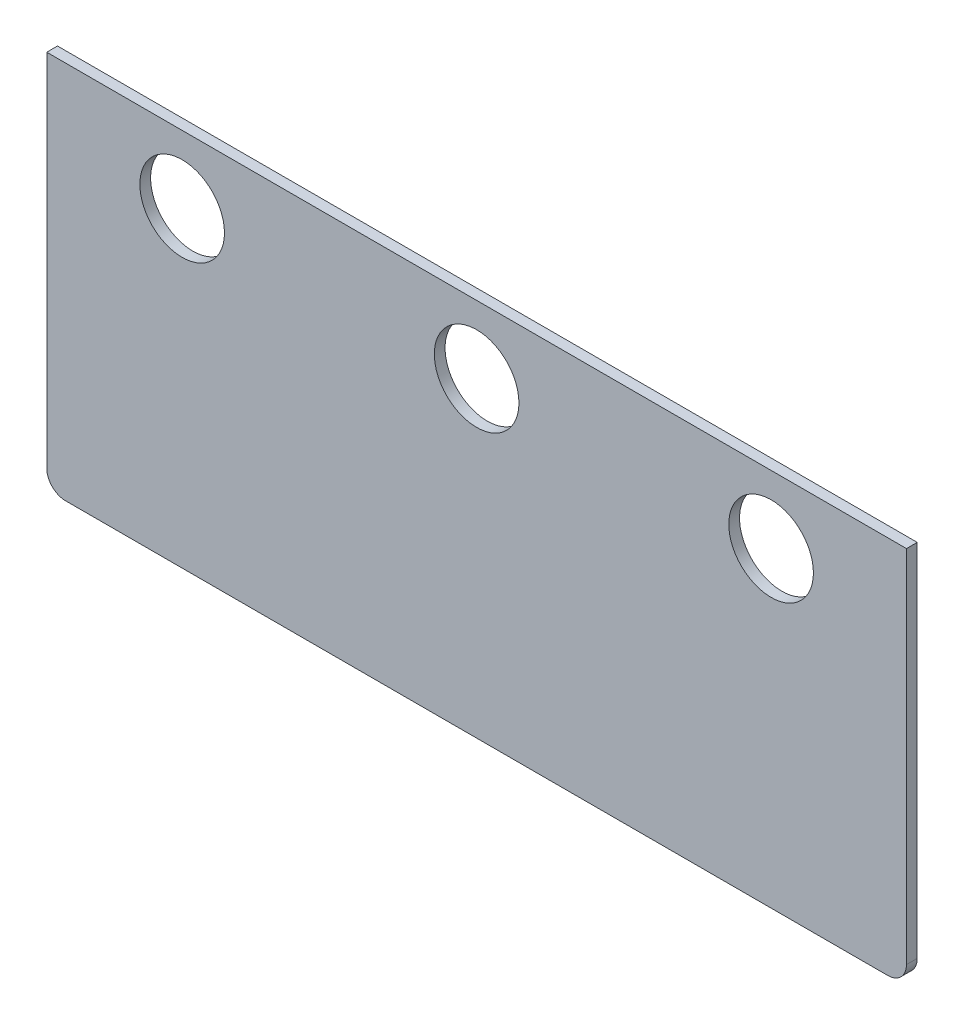
SolidWorks part; units mm, degrees
material "5052-H32"
ref_plane "Front Plane" through (0, 0, 0) normal (0, 0, 1) x (1, 0, 0)
ref_plane "Top Plane" through (0, 0, 0) normal (0, 1, 0) x (1, 0, 0)
ref_plane "Right Plane" through (0, 0, 0) normal (1, 0, 0) x (0, 0, -1)
sketch "Sketch1" plane through (0, 0, 0) normal (0, 0, 1) x (1, 0, 0)
  line L0 (-127, 112) -> (-127, 0)
  line L2 (127, 0) -> (127, 112)
  line L3 (127, 112) -> (-127, 112)
  line L4 (-127, 0) -> (127, 0)
  circle A0 centre (87, 92) radius 12.5
  circle A1 centre (0, 92) radius 12.5
  circle A2 centre (-87, 92) radius 12.5
  point P3 (-127.6556, 0)
  point P10 (122.0561, 0)
  point P11 (0, 112)
  point P12 (123.5408, 0)
  point P22 (0, 0)
  dimension "D4" = 25
  dimension "D1" = 112
  dimension "D2" = 254
  dimension "D3" = 20
  dimension "D5" = 40
  dimension "D6" = 40
extrude "Boss-Extrude1" add sketch "Sketch1" along normal blind 3.175
fillet "Fillet1" radius 5.5562 2 edges at (127, 0, 1.5875) (-127, 0, 1.5875)
equation "\"L\"= 420mm"
equation "\"W\"= 255mm"
equation "\"H\"= 110mm"
equation "\"Compartment Width\"= 80"
equation "\"T\"= 4.7625 * 2 / 3mm"
equation "\"Inside Fillet Radius\"= 5.55625mm"
equation "\"D1@Boss-Extrude1\"=\"T\""
equation "\"Hole\"=25mm"
equation "\"D4@Sketch1\"=\"Hole\""
equation "\"D2@Sketch1\"=\"W\"-1"
equation "\"D1@Sketch1\"=\"H\"+\"T\"-1.175"
equation "\"D1@Fillet1\"=\"Inside Fillet Radius\""
